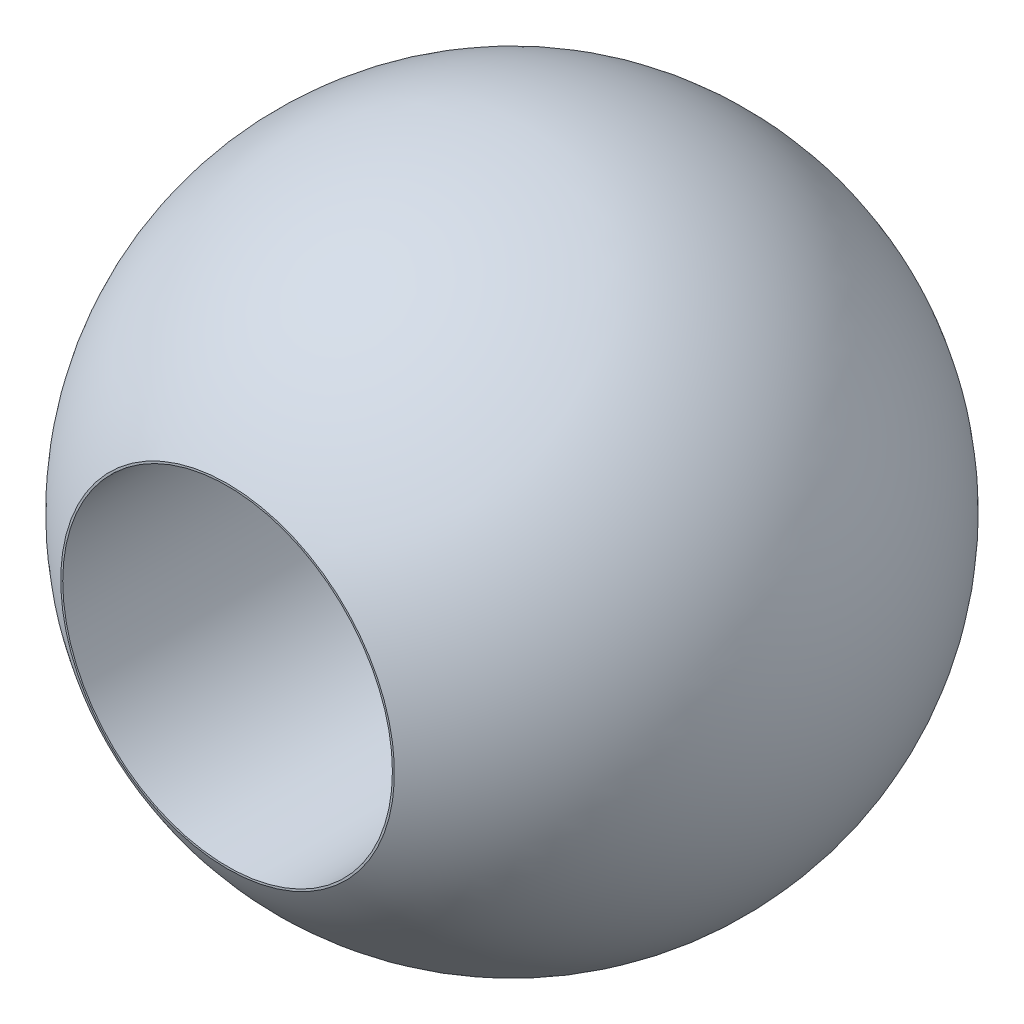
SolidWorks part; units mm, degrees
ref_plane "Front" through (0, 0, 0) normal (0, 0, 1) x (1, 0, 0)
ref_plane "Top" through (0, 0, 0) normal (0, 1, 0) x (1, 0, 0)
ref_plane "Right" through (0, 0, 0) normal (1, 0, 0) x (0, 0, -1)
sketch "Sketch1" plane through (0, 0, 0) normal (0, 0, 1) x (1, 0, 0)
  line L0 (0, 0) -> (0, -14)
  line L1 (0, -14) -> (2, -14)
  line L2 (2, -14) -> (2, 0)
  line L3 (2, 0) -> (0, 0)
  line L5 (0, 16.5) -> (0, 0) construction
  line L6 (0, 16.5) -> (5.5, 16.5) construction
  line L7 (5.5, 16.5) -> (5.5, 11) construction
  line L8 (-2, -14) -> (-2, 0) construction
  line L9 (5.5, 16.4) -> (0, 16.4) construction
  arc A0 (4.4887, 7.8218) -> (0, 16.5) centre (0, 11) ccw construction
  circle A1 centre (0, 11) radius 2 construction
  circle A2 centre (0, 11) radius 4 construction
  circle A3 centre (0, 11) radius 4.04 construction
  arc A4 (2, 0) -> (4.4887, 7.8218) centre (15.5357, 0) cw construction
  point P16 (-2, -9.975)
  dimension "A" = 4
  dimension "Ball Dia" = 8
  dimension "B" = 11
  dimension "D1" = 8.08
  dimension "D" = 25
  dimension "E" = 14
  dimension "Thread Dia" = 4
  dimension "D2" = 4.025
  dimension "D3" = 30.4
revolve "Revolve1" add sketch "Sketch1" angle 360 about L5
sketch "Sketch12" plane through (0, -14, 0) normal (0, -1, 0) x (1, 0, 0)
  circle A1 centre (0, 0) radius 2
  circle A2 centre (0, 0) radius 2
  dimension "D1" = 0
curve "Helix/Spiral1" pitch 0.7 height 14.7 turns 21 parameters "pitch"=0.7
chamfer "Chamfer2" distance 0.7 angle 45 1 edges at (-2, -14, 0)
sketch "Sketch13" plane through (0, 0, 0) normal (1, 0, 0) x (0, 0, -1)
  line L0 (-2, -14.6125) -> (-2, -14)
  line L1 (-2, -14) -> (-1.5453, -14.2625)
  line L2 (-1.5453, -14.2625) -> (-1.5453, -14.35)
  line L3 (-1.5453, -14.35) -> (-2, -14.6125)
  line L4 (-1.5453, -14.3063) -> (-2, -14.3063) construction
  line L5 (-1.7727, -14.4813) -> (-1.7727, -14.1313) construction
  line L6 (-2, -14) -> (2, -14) construction
  dimension "D1" = 60
  dimension "D3" = 0.35
sweep "Cut-Sweep1" cut profiles "Sketch13" path "Helix/Spiral1" align with end faces yes
sketch "Sketch4" plane through (0, 0, 0) normal (0, 0, 1) x (1, 0, 0)
  line L0 (2, 0) -> (0, 0) construction
  line L2 (0, 16.5) -> (0, 0) construction
  line L3 (2, 0) -> (0, 0)
  line L5 (0, 16.5) -> (0, 0)
  line L6 (0, 16.5) -> (0, 19.04) construction
  arc A0 (4.4887, 7.8218) -> (0, 16.5) centre (0, 11) ccw construction
  arc A1 (4.4887, 7.8218) -> (0, 16.5) centre (0, 11) ccw
  arc A2 (4.4887, 7.8218) -> (2, 0) centre (15.5357, 0) ccw construction
  arc A3 (4.4887, 7.8218) -> (2, 0) centre (15.5357, 0) ccw
  dimension "D1" = 2.54
revolve "Revolve2" add sketch "Sketch4" angle 360 about L6
sketch "Sketch5" plane through (0, 0, 0) normal (1, 0, 0) x (0, 0, -1)
  line L0 (2.25, 16.5) -> (5.5, 16.5)
  line L1 (-2.25, 16.5) -> (2.25, 16.5) construction
  line L2 (-2.25, 16.5) -> (-2.25, 0.9)
  line L3 (-2, 0) -> (2, 0) construction
  line L4 (2.25, 16.5) -> (2.25, 0.9)
  line L5 (5.5, 16.5) -> (5.5, 0)
  line L6 (5.5, 0) -> (2, 0)
  line L7 (-2, 0) -> (-5.5, 0)
  line L8 (-5.5, 0) -> (-5.5, 16.5)
  line L9 (-5.5, 16.5) -> (-2.25, 16.5)
  line L10 (2, 0) -> (2.25, 0.9)
  line L11 (-2, 0) -> (-2.25, 0.9)
  line L12 (-2.25, 0.9) -> (2.25, 0.9) construction
  line L13 (0, 0) -> (0, 0.9) construction
  arc A0 (4.4887, 7.8218) -> (-4.4887, 7.8218) centre (0, 11) ccw construction
  dimension "F" = 4.5
  dimension "D2" = 0.9
  dimension "D1" = 4
extrude "Cut-Extrude1" cut sketch "Sketch5" against normal through all and the other way through all
sketch "Sketch6" plane through (0, 0, 0) normal (0, 0, 1) x (1, 0, 0)
  circle A0 centre (0, 11) radius 4.04 construction
  circle A1 centre (0, 11) radius 4.04
extrude "Cut-Extrude2" cut sketch "Sketch6" against normal through all and the other way through all
sketch "Sketch7" plane through (0, 0, 0) normal (0, 0, 1) x (1, 0, 0)
  line L0 (0, 15) -> (0, 7)
  line L1 (0, 16.5) -> (0, 0) construction
  line L2 (0, 0) -> (0, 7) construction
  arc A0 (0, 7) -> (0, 15) centre (0, 11) ccw
  circle A1 centre (0, 11) radius 4 construction
revolve "Revolve3" add sketch "Sketch7" angle 360 about L2
sketch "Sketch8" plane through (0, 0, 0) normal (1, 0, 0) x (0, 0, -1)
  line L0 (-2.25, 16.5) -> (2.25, 16.5) construction
  line L1 (-3.45, 16.5) -> (3.45, 16.5) construction
  line L2 (-3.45, 16.5) -> (-3.45, 0)
  line L3 (-3.45, 0) -> (3.45, 0) construction
  line L4 (3.45, 16.5) -> (3.45, 0)
  line L5 (3.45, 16.5) -> (5.5, 16.5)
  line L6 (5.5, 16.5) -> (5.5, 0)
  line L7 (5.5, 0) -> (3.45, 0)
  line L8 (-3.45, 0) -> (-5.5, 0)
  line L9 (-5.5, 0) -> (-5.5, 16.5)
  line L10 (-5.5, 16.5) -> (-3.45, 16.5)
  dimension "C" = 6.9
extrude "Cut-Extrude3" cut sketch "Sketch8" against normal through all and the other way through all
sketch "Sketch10" plane through (0, 0, 0) normal (0, 0, 1) x (1, 0, 0)
  circle A0 centre (0, 11) radius 2 construction
  circle A1 centre (0, 11) radius 2
extrude "Cut-Extrude4" cut sketch "Sketch10" against normal through all and the other way through all
chamfer "Chamfer1" [suppressed] distance 0.2 angle 45
sketch "Sketch11" plane through (0, 0, 0) normal (1, 0, 0) x (0, 0, -1)
  line L0 (0, 11) -> (-3.45, 11.9244) construction
  line L1 (2.25, 11) -> (-2.25, 11) construction
  line L2 (0, 11) -> (-3.45, 10.0756) construction
  line L3 (0, 16.5) -> (0, 0) construction
  line L4 (-3.45, 16.5) -> (-3.45, 0) construction
  line L5 (0, 11) -> (0.0074, 11) construction
  dimension "Swivel" = 30
sketch "Sketch14" plane through (0, 0, 0) normal (0, 0, 1) x (1, 0, 0)
  line L1 (5.5, 16.5) -> (-5.5, 16.5)
  line L2 (5.5, 16.5) -> (5.5, 16.4)
  line L3 (5.5, 16.4) -> (-5.5, 16.4)
  line L4 (-5.5, 16.5) -> (-5.5, 16.4)
extrude "Cut-Extrude5" cut sketch "Sketch14" against normal through all both and the other way through all
delete or keep bodies "Body-Delete/Keep 1" type delete bodies bodies 119
delete or keep bodies "Body-Delete/Keep 2" [suppressed] type delete bodies bodies 116
equation "\"D1@Sketch1\"=\"Ball Dia@Sketch1\"*1.01"
equation "\"D1@Chamfer1\"=\"A@Sketch1\"/20"
equation "\"D1@Sketch5\"=\"Thread Dia@Sketch1\""
equation "\"D2@Sketch5\"=\"F@Sketch5\"/5"
equation "\"D2@Sketch13\" = \"pitch@Helix/Spiral1\"*.125"
equation "\"D3@Sketch13\" = \"pitch@Helix/Spiral1\"*.50"
equation "\"D3@Helix/Spiral1\" = \"E@Sketch1\"+\"pitch@Helix/Spiral1\""
equation "\"D1@Chamfer2\" = \"pitch@Helix/Spiral1\""
equation "\"D2@Sketch1\" = \"pitch@Helix/Spiral1\"*5.75"
